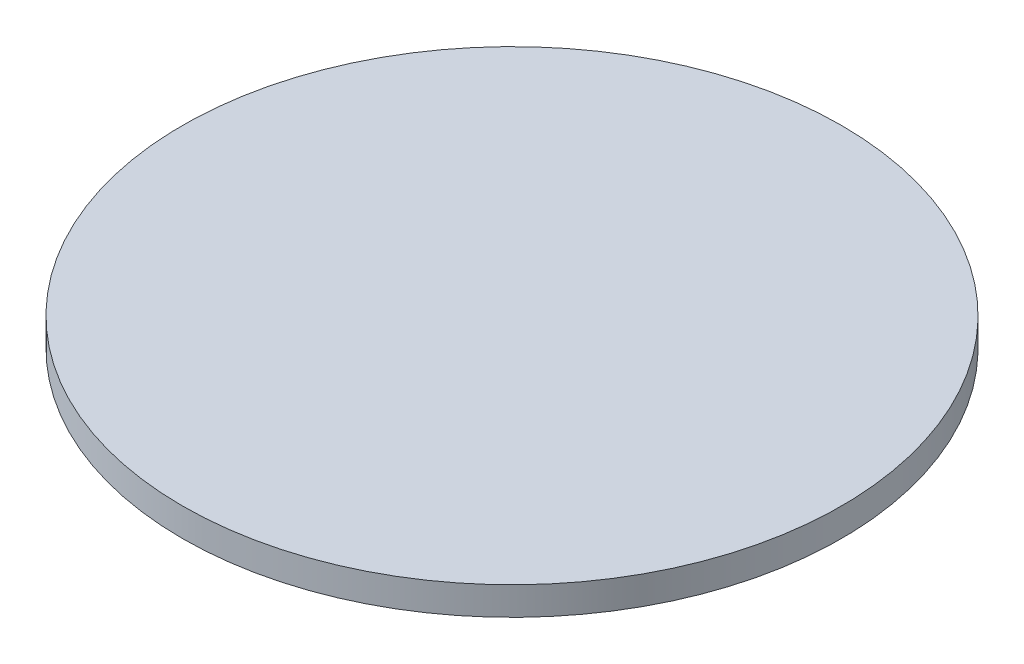
SolidWorks part; units mm, degrees
ref_plane "Front Plane" through (0, 0, 0) normal (0, 0, 1) x (1, 0, 0)
ref_plane "Top Plane" through (0, 0, 0) normal (0, 1, 0) x (1, 0, 0)
ref_plane "Right Plane" through (0, 0, 0) normal (1, 0, 0) x (0, 0, -1)
sketch "Sketch1" plane through (0, 0, 0) normal (0, 1, 0) x (1, 0, 0)
  line L1 (0, 50) -> (-90, 50) construction
  line L2 (0, 50) -> (0, -50) construction
  line L3 (0, -50) -> (-90, -50) construction
  line L4 (-90, 50) -> (-90, -50) construction
  line L5 (-87, 0) -> (0, 0) construction
  circle A0 centre (-45, 0) radius 35
  circle A2 centre (-45, 0) radius 6 construction
  circle A3 centre (-45, 0) radius 2.5 construction
  point P4 (0, 0)
  point P8 (-44.0703, 9.1001)
  point P14 (0, 0)
  dimension "D4" = 70
  dimension "D5" = 12
  dimension "D6" = 5
  dimension "D1" = 100
  dimension "D2" = 90
  dimension "D3" = 45
extrude "Boss-Extrude1" add sketch "Sketch1" along normal blind 3
